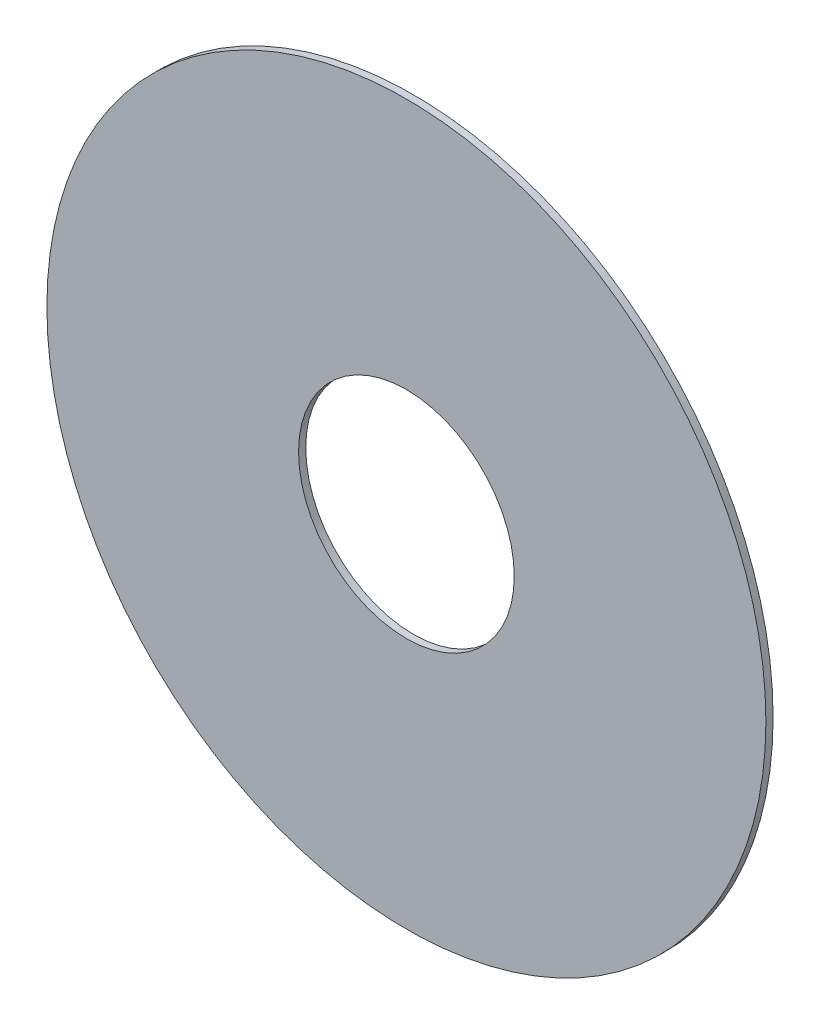
SolidWorks part; units mm, degrees
ref_plane "Front Plane" through (0, 0, 0) normal (0, 0, 1) x (1, 0, 0)
ref_plane "Top Plane" through (0, 0, 0) normal (0, 1, 0) x (1, 0, 0)
ref_plane "Right Plane" through (0, 0, 0) normal (1, 0, 0) x (0, 0, -1)
sketch "Sketch1" plane through (0, 0, 0) normal (0, 0, 1) x (1, 0, 0)
  circle A0 centre (0, 0) radius 30
  circle A1 centre (0, 0) radius 100
  dimension "D1" = 60
  dimension "D2" = 200
base flange "Base-Flange1" sketch "Sketch1" thickness 2 reverse thickness direction no parameters "D1"=0.75
sketch "Bend-Lines1" [suppressed] plane through (0, 0, 0) normal (0, 1, 0) x (1, 0, 0)
sketch "Bounding-Box1" [suppressed] plane through (0, 0, 0) normal (0, 1, 0) x (1, 0, 0)
sheet metal parameters "Sheet-Metal1" thickness 2 parameters "D1"=0.75
flat pattern "Flat-Pattern1" [suppressed]
sketch "Bend-Lines2" plane through (0, 0, 0) normal (0, 1, 0) x (1, 0, 0)
sketch3d "Bounding-Box2" [suppressed]
  line L0 (-99.8748, 100.1249, 0) -> (-100.1248, -99.8749, 0) construction
  line L1 (100.1249, 99.8749, 0) -> (99.8749, -100.1249, 0) construction
  line L2 (-99.8748, 100.1249, 0) -> (100.1249, 99.8749, 0) construction
  line L3 (-100.1248, -99.8749, 0) -> (99.8749, -100.1249, 0) construction
